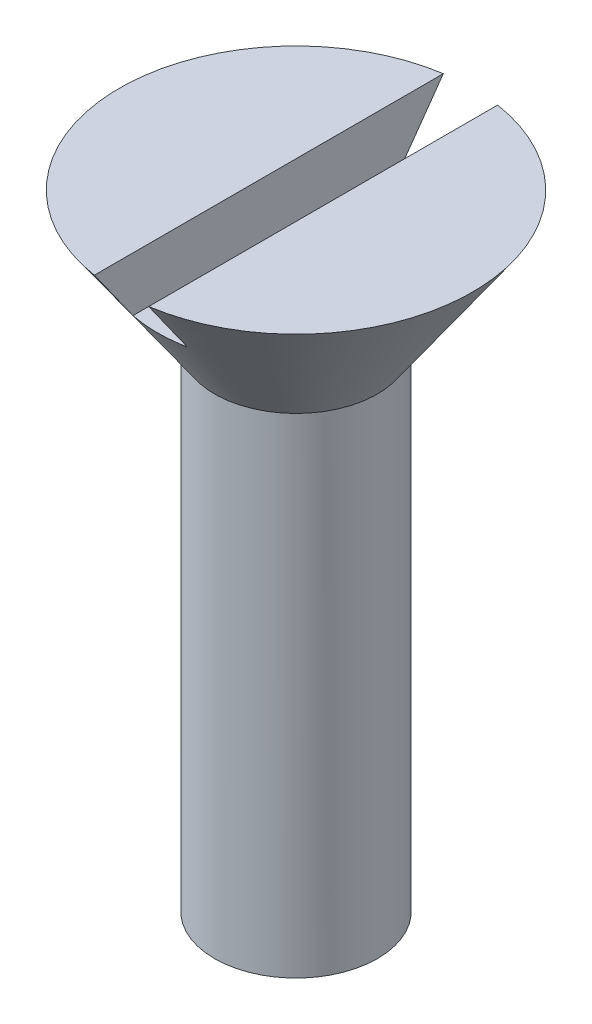
SolidWorks part; units mm, degrees
ref_plane "Front Plane" through (0, 0, 0) normal (0, 0, 1) x (1, 0, 0)
ref_plane "Top Plane" through (0, 0, 0) normal (0, 1, 0) x (1, 0, 0)
ref_plane "Right Plane" through (0, 0, 0) normal (1, 0, 0) x (0, 0, -1)
sketch "Sketch1" plane through (0, 0, 0) normal (0, 0, 1) x (1, 0, 0)
  line L1 (0, -1.7321) -> (3, 0)
  line L2 (3, 0) -> (3, 18)
  line L3 (3, 18) -> (6.5, 23)
  line L4 (6.5, 23) -> (-6.5, 23)
  line L5 (3, 0) -> (0, 0)
  line L6 (0, -1.7321) -> (0, 0)
  line L7 (0, 0) -> (0, 18)
  line L8 (0, 18) -> (0, 23)
  line L9 (3, 18) -> (0, 18)
  line L10 (1, 23) -> (1, 21)
  line L11 (1, 21) -> (-1, 21)
  line L12 (-1, 23) -> (-1, 21)
  point P12 (0, 21)
  dimension "D1" = 5
  dimension "D2" = 18
  dimension "D3" = 6.5
  dimension "D4" = 3
  dimension "D5" = 60
  dimension "D6" = 2
  dimension "D7" = 1
revolve "Revolve1" add sketch "Sketch1" angle 360 about L8 region at (1, -0.5774, 0) region at (1.5, 9, 0) region at (2.6648, 20.6973, 0) region at (0.5, 22, 0)
extrude "Cut-Extrude1" cut sketch "Sketch1<3>" against normal through all both and the other way through all contours L4 L12 L11 L8 | L11 L10 L4 L8 region at (-0.5, 22, 0) region at (0.5, 22, 0)
sketch "Sketch1<3>" plane through (0, 0, 0) normal (0, 0, 1) x (1, 0, 0) same geometry as "Sketch1"
